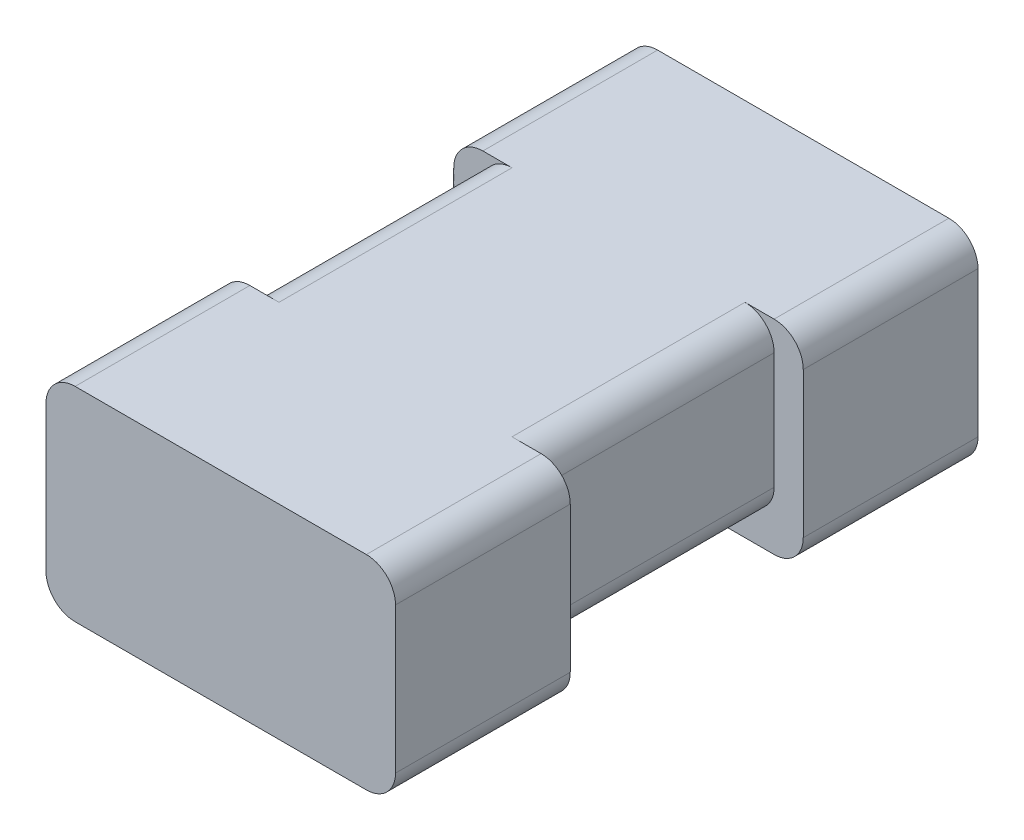
SolidWorks part; units mm, degrees
ref_plane "Front Plane" through (0, 0, 0) normal (0, 0, 1) x (1, 0, 0)
ref_plane "Top Plane" through (0, 0, 0) normal (0, 1, 0) x (1, 0, 0)
ref_plane "Right Plane" through (0, 0, 0) normal (1, 0, 0) x (0, 0, -1)
sketch "Sketch2" plane through (0, 0, 0) normal (0, 0, 1) x (1, 0, 0)
  line L1 (0, 0) -> (0.5, 0)
  line L2 (0, 0) -> (0, -0.3)
  line L3 (0, -0.3) -> (0.5, -0.3)
  line L4 (0.5, 0) -> (0.5, -0.3)
  point P4 (0, 0)
  dimension "D1" = 0.5
  dimension "D2" = 0.3
extrude "Boss-Extrude1" add sketch "Sketch2" along normal blind 0.4
sketch "Sketch3" plane through (0, 0, 0.4) normal (0, 0, 1) x (1, 0, 0)
  line L0 (0, -0.3) -> (0.5, -0.3) construction
  line L1 (-0.05, 0) -> (0.55, 0)
  line L2 (-0.05, 0) -> (-0.05, -0.35)
  line L3 (-0.05, -0.35) -> (0.55, -0.35)
  line L4 (0.55, 0) -> (0.55, -0.35)
  line L5 (0.5, 0) -> (0, 0) construction
  point P6 (0.25, -0.3)
  point P7 (0.25, -0.35)
  dimension "D1" = 0.6
  dimension "D2" = 0.35
extrude "Boss-Extrude2" add sketch "Sketch3" along normal blind 0.3
sketch "Sketch4" plane through (0, 0, 0) normal (0, 0, -1) x (-1, 0, 0)
  line L0 (0.05, 0) -> (0.05, -0.35) construction
  line L1 (-0.55, 0) -> (0.05, 0)
  line L2 (-0.55, 0) -> (-0.55, -0.35)
  line L3 (-0.55, -0.35) -> (0.05, -0.35)
  line L4 (0.05, 0) -> (0.05, -0.35)
  line L5 (-0.55, -0.35) -> (-0.55, 0) construction
  line L6 (0.05, -0.35) -> (-0.55, -0.35) construction
  line L7 (-0.5, 0) -> (0, 0) construction
extrude "Boss-Extrude4" add sketch "Sketch4" along normal blind 0.3
fillet "Fillet2" radius 0.05 12 edges at (0.55, -0.35, 0.55) (-0.05, -0.35, 0.55) (-0.05, -0.35, -0.15) (0.55, -0.35, -0.15) (0.5, -0.3, 0.2) (0, -0.3, 0.2) (0.55, 0, 0.55) (-0.05, 0, 0.55) (0, 0, 0.2) (0.5, 0, 0.2) (0.55, 0, -0.15) (-0.05, 0, -0.15)
